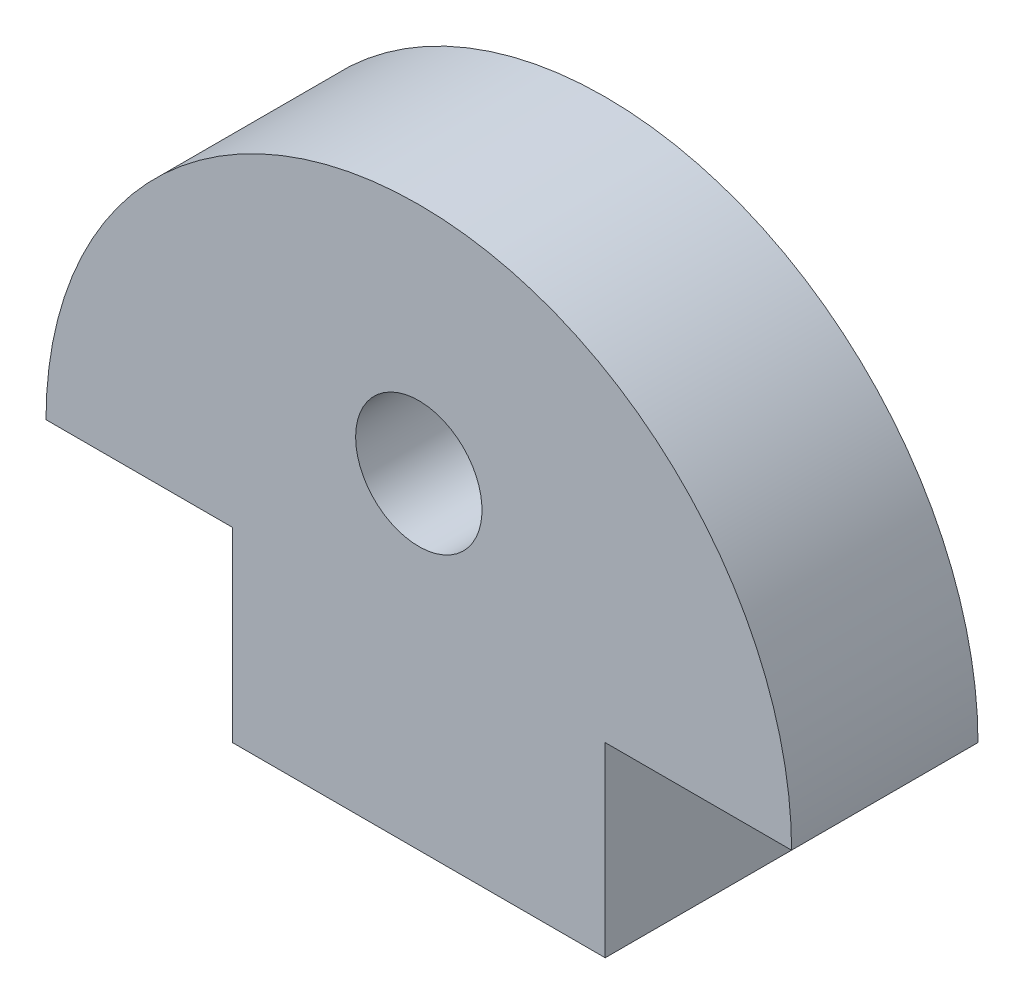
SolidWorks part; units mm, degrees
material "Custom Plastic"
ref_plane "Front Plane" through (0, 0, 0) normal (0, 0, 1) x (1, 0, 0)
ref_plane "Top Plane" through (0, 0, 0) normal (0, 1, 0) x (1, 0, 0)
ref_plane "Right Plane" through (0, 0, 0) normal (1, 0, 0) x (0, 0, -1)
sketch "Sketch1" plane through (0, 0, 0) normal (0, 0, 1) x (1, 0, 0)
  line L1 (-12.7, -12.7) -> (12.7, -12.7)
  line L2 (-12.7, -12.7) -> (-12.7, 12.7) construction
  line L3 (-12.7, 12.7) -> (12.7, 12.7) construction
  line L4 (12.7, -12.7) -> (12.7, 12.7) construction
  line L5 (-12.7, -12.7) -> (12.7, 12.7) construction
  line L6 (-12.7, 12.7) -> (12.7, -12.7) construction
  arc A0 (-12.7, -12.7) -> (12.7, -12.7) centre (0, -12.7) cw
  point P0 (0, 0)
  dimension "D1" = 25.4
  dimension "D2" = 25.4
extrude "Base" add sketch "Sketch1" along normal blind 6.35
sketch "Axle hole placement" plane through (0, 0, 6.35) normal (0, 0, 1) x (1, 0, 0)
  line L0 (-12.7, -7.9375) -> (12.7, -7.9375) construction
  line L3 (0, 0) -> (0, -12.7) construction
  line L4 (-12.7, -12.7) -> (12.7, -12.7) construction
  line L5 (-12.7, -12.7) -> (12.7, -12.7) construction
  line L7 (-12.7, -12.7) -> (12.7, -12.7) construction
  arc A0 (12.7, -12.7) -> (-12.7, -12.7) centre (0, -12.7) ccw construction
  point P12 (0, -7.9375)
  dimension "D1" = 4.7625
hole_wizard "Axle hole" positions "Sketch5" profile "Sketch4" hole size "#8" standard "ANSI Inch" end condition through all
sketch "Sketch5" plane through (0, 0, 0) normal (0, 0, -1) x (-1, 0, 0)
  point P3 (0, -7.9375)
sketch "Sketch4" plane through (0, -7.9375, 0) normal (1, 0, 0) x (0, 1, 0)
  line L0 (0, 0) -> (0, 6.35)
  line L1 (0, 6.35) -> (2.1526, 6.35)
  line L2 (2.1526, 6.35) -> (2.1526, 0)
  line L5 (2.1526, 0) -> (0, 0)
  line L11 (0, -6.35) -> (0, 107.95) construction
  dimension "Thru Hole Dia." = 4.3053
  dimension "Thru Hole Depth" = 6.35
sketch "Sketch8" plane through (0, 0, 6.35) normal (0, 0, 1) x (1, 0, 0)
  line L0 (-12.7, -12.7) -> (12.7, -12.7) construction
  line L1 (-6.35, -12.7) -> (6.35, -12.7)
  line L2 (-6.35, -12.7) -> (-6.35, -19.05)
  line L3 (-6.35, -19.05) -> (6.35, -19.05)
  line L4 (6.35, -12.7) -> (6.35, -19.05)
  point P6 (0, -12.7)
  dimension "D1" = 12.7
  dimension "D2" = 6.35
extrude "Boss-Extrude2" add sketch "Sketch8" against normal blind 6.35
equation "\"MAT_THICKNESS\"=0.25"
equation "\"D1@Base\"=\"MAT_THICKNESS\""
equation "\"D2@Sketch8\"=\"MAT_THICKNESS\""
equation "\"D1@Boss-Extrude2\"=\"MAT_THICKNESS\""
